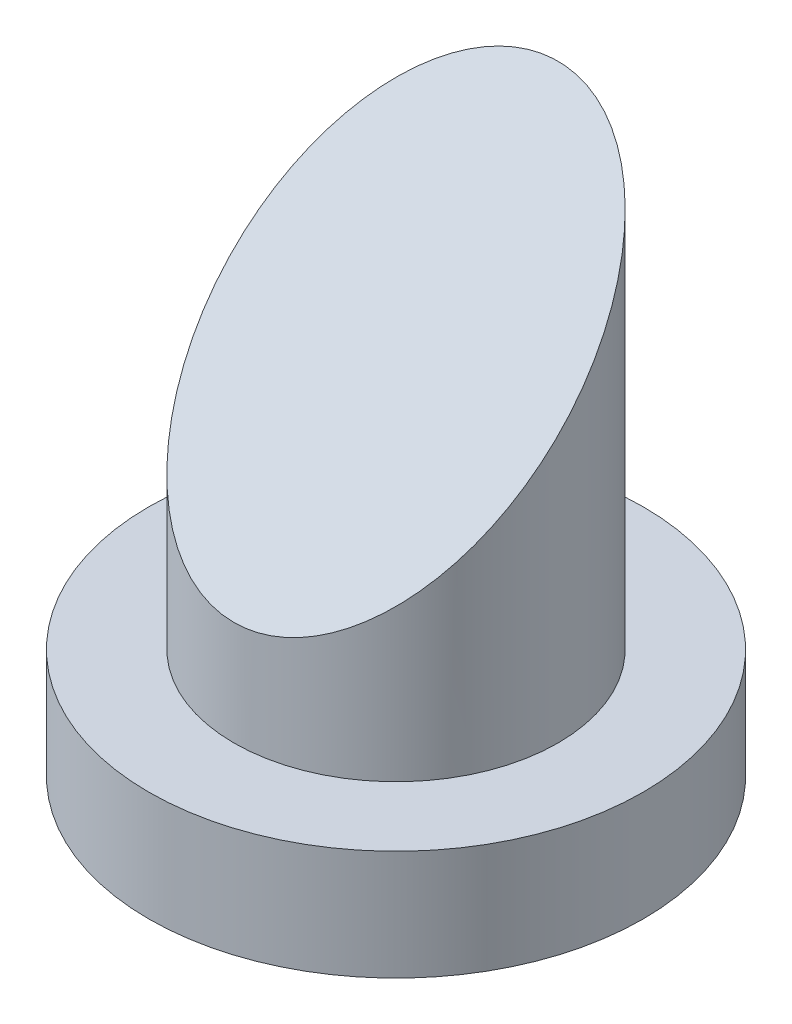
SolidWorks part; units mm, degrees
material "PTFE (general)"
ref_plane "Front Plane" through (0, 0, 0) normal (0, 0, 1) x (1, 0, 0)
ref_plane "Top Plane" through (0, 0, 0) normal (0, 1, 0) x (1, 0, 0)
ref_plane "Right Plane" through (0, 0, 0) normal (1, 0, 0) x (0, 0, -1)
sketch "Sketch1" plane through (0, 0, 0) normal (0, 1, 0) x (1, 0, 0)
  circle A0 centre (0, 0) radius 9
  dimension "D1" = 18
extrude "Boss-Extrude1" add sketch "Sketch1" along normal blind 4
sketch "Sketch2" plane through (0, 4, 0) normal (0, 1, 0) x (1, 0, 0)
  circle A0 centre (0, 0) radius 5.9
  dimension "D1" = 11.8
extrude "Boss-Extrude2" add sketch "Sketch2" along normal blind 20
sketch "Sketch3" plane through (0, 0, 0) normal (1, 0, 0) x (0, 0, -1)
  line L0 (-6.28, 7.42) -> (6.28, 19.98)
  line L2 (9, 4) -> (-9, 4) construction
  line L4 (-6.28, 7.42) -> (-6.28, 28.7719)
  line L5 (-6.28, 28.7719) -> (6.28, 28.7719)
  line L6 (6.28, 19.98) -> (6.28, 28.7719)
  point P2 (0, 13.7)
  dimension "D1" = 12.56
  dimension "D2" = 45
  dimension "D3" = 12.56
  dimension "D4" = 6.28
  dimension "D5" = 9.7
extrude "Cut-Extrude1" cut sketch "Sketch3" against normal through all both and the other way through all contours L0 L6 L5 L4 region at (0, 20.7998, 0.8722)
sketch "Sketch4" plane through (0, 0, 0) normal (0, -1, 0) x (1, 0, 0)
  circle A0 centre (0, -6) radius 0.425
  dimension "D1" = 0.85
  dimension "D2" = 6
extrude "Cut-Extrude2" cut sketch "Sketch4" against normal blind 1.5
